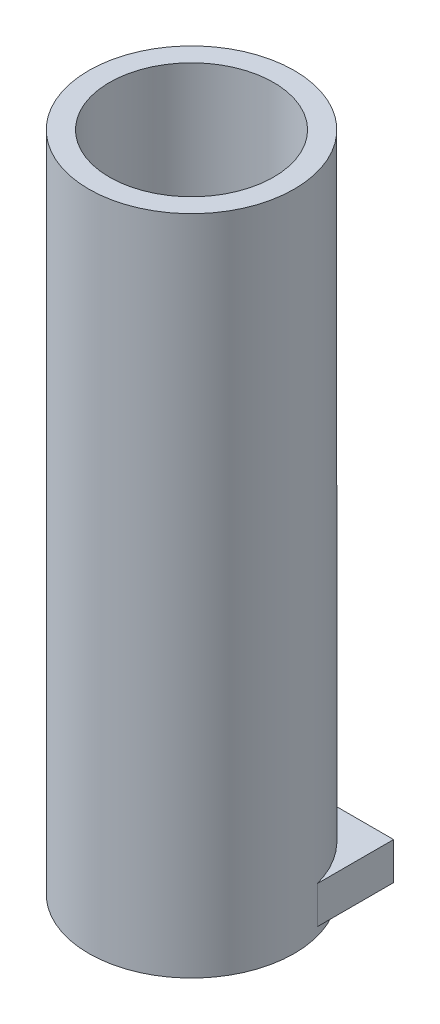
SolidWorks part; units mm, degrees
ref_plane "Front Plane" through (0, 0, 0) normal (0, 0, 1) x (1, 0, 0)
ref_plane "Top Plane" through (0, 0, 0) normal (0, 1, 0) x (1, 0, 0)
ref_plane "Right Plane" through (0, 0, 0) normal (1, 0, 0) x (0, 0, -1)
sketch "Sketch1" plane through (0, 0, 0) normal (0, 1, 0) x (1, 0, 0)
  circle A0 centre (0, 0) radius 12.4187
  circle A1 centre (0, 0) radius 9.9187
  dimension "D1" = 24.8374
  dimension "D2" = 19.8374
extrude "Boss-Extrude1" add sketch "Sketch1" against normal blind 80 contours A0
extrude "Cut-Extrude1" cut sketch "Sketch1<3>" against normal blind 20 contours A1
sketch "Sketch1<3>" plane through (0, 0, 0) normal (0, 1, 0) x (1, 0, 0) same geometry as "Sketch1"
ref_axis "Axis1" through (0, -80, 0) along (0, 1, 0)
ref_plane "Plane1" through (0, 0, -12.4187) normal (0, 0, -1) x (-1, 0, 0)
sketch "Sketch2" plane through (0, 0, -12.4187) normal (0, 0, 1) x (1, 0, 0)
  line L0 (-12.4187, -80) -> (12.4187, -80) construction
  line L1 (-12.4187, -80) -> (12.4187, -80)
  line L2 (12.4187, -80) -> (12.4187, 0) construction
  line L3 (12.4187, -80) -> (12.4187, 0) construction
  line L4 (-12.4187, 0) -> (-12.4187, -80) construction
  line L5 (-12.4187, 0) -> (-12.4187, -80) construction
  line L6 (-12.4187, -74.4872) -> (12.4187, -74.4872)
  line L9 (-12, -80) -> (-12, -74.4872)
  line L10 (12, -74.4872) -> (12, -80)
  line L11 (0, -80) -> (0, 0) construction
  line L12 (-12.4187, -79) -> (12.4187, -79)
  dimension "D1" = 12
  dimension "D2" = 12
  dimension "D3" = 1
extrude "Boss-Extrude2" add sketch "Sketch2" along normal up to surface (6.6547 mm away) contours L12 L9 L6 L10 region at (0, -76.7436, -12.4187) up to face at (0, -80, 12.4187)
sketch "Sketch3" plane through (0, 0, -12.4187) normal (0, 0, -1) x (-1, 0, 0)
  line L0 (0, -79) -> (0, -74.4872) construction
  line L2 (-12, -76.7436) -> (12, -76.7436) construction
  line L3 (-12, -74.4872) -> (-12, -79) construction
  line L4 (12, -79) -> (12, -74.4872) construction
  circle A0 centre (-4.45, -76.7436) radius 0.6
  circle A1 centre (-6.45, -76.7436) radius 0.6
  circle A2 centre (-8.45, -76.7436) radius 0.6
  circle A3 centre (-10.45, -76.7436) radius 0.6
  circle A4 centre (10.45, -76.7436) radius 0.6
  circle A5 centre (8.45, -76.7436) radius 0.6
  circle A6 centre (6.45, -76.7436) radius 0.6
  circle A7 centre (4.45, -76.7436) radius 0.6
  point P20 (0, 0)
  dimension "D1" = 1.2
  dimension "D3" = 4.45
  dimension "D2" = 4
extrude "Cut-Extrude2" cut sketch "Sketch3" against normal blind 10
equation "\"D1@Sketch1\"=\"D2@Sketch1\"+0.5"
equation "\"D2@Sketch2\"=\"D1@Sketch2\""
